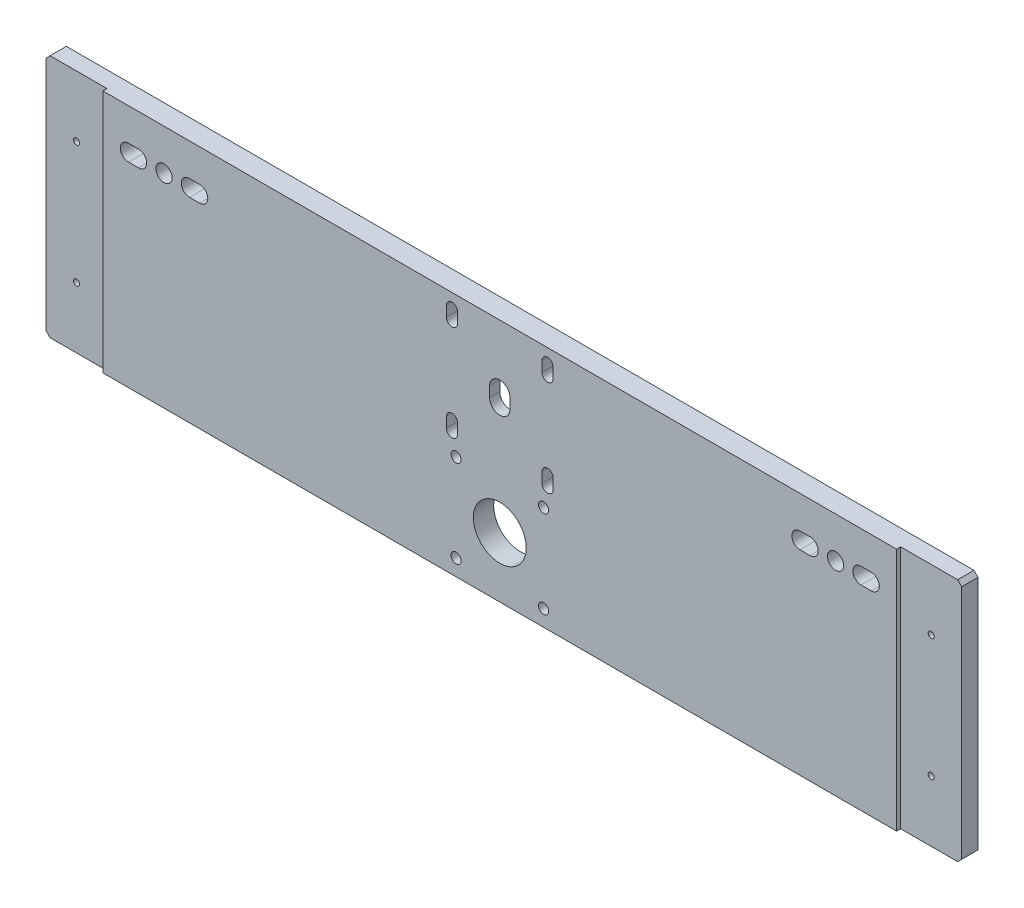
SolidWorks part; units mm, degrees
ref_plane "Piano frontale" through (0, 0, 0) normal (0, 0, 1) x (1, 0, 0)
ref_plane "Piano superiore" through (0, 0, 0) normal (0, 1, 0) x (1, 0, 0)
ref_plane "Piano destro" through (0, 0, 0) normal (1, 0, 0) x (0, 0, -1)
sketch "Schizzo1" plane through (0, 0, 0) normal (0, 0, 1) x (1, 0, 0)
  line L0 (225, 120) -> (225, 0) construction
  line L1 (2, 0) -> (448, 0)
  line L2 (0, 2) -> (0, 118)
  line L3 (2, 120) -> (448, 120)
  line L4 (450, 2) -> (450, 118)
  line L5 (203.5, 52.7163) -> (203.5, 5.9855) construction
  line L6 (250.0723, 51) -> (199.9971, 51) construction
  line L7 (225, 29.5) -> (243.5099, 29.5) construction
  line L8 (459.2931, 100) -> (370.8276, 100) construction
  line L9 (407.5, 100) -> (402.5, 100) construction
  line L10 (407.5, 96) -> (402.5, 96)
  line L11 (407.5, 104) -> (402.5, 104)
  line L12 (377.5, 100) -> (372.5, 100) construction
  line L13 (377.5, 96) -> (372.5, 96)
  line L14 (377.5, 104) -> (372.5, 104)
  line L15 (42.5, 100) -> (47.5, 100) construction
  line L16 (42.5, 96) -> (47.5, 96)
  line L17 (42.5, 104) -> (47.5, 104)
  line L18 (72.5, 100) -> (77.5, 100) construction
  line L19 (72.5, 96) -> (77.5, 96)
  line L20 (72.5, 104) -> (77.5, 104)
  line L21 (0, 118) -> (2, 120)
  line L22 (2, 0) -> (0, 2)
  line L23 (448, 0) -> (450, 2)
  line L24 (448, 120) -> (450, 118)
  line L25 (225, 60) -> (450, 60) construction
  line L26 (267.1703, 87) -> (188.4108, 87) construction
  line L27 (225, 84.5) -> (225, 89.5) construction
  line L28 (220, 84.5) -> (220, 89.5)
  line L29 (230, 84.5) -> (230, 89.5)
  line L30 (201.5, 113.1) -> (201.5, 108.1) construction
  line L31 (204.25, 113.1) -> (204.25, 108.1)
  line L32 (198.75, 113.1) -> (198.75, 108.1)
  line L33 (248.5, 113.1) -> (248.5, 108.1) construction
  line L34 (245.75, 113.1) -> (245.75, 108.1)
  line L35 (251.25, 113.1) -> (251.25, 108.1)
  line L36 (201.5, 60.9) -> (201.5, 65.9) construction
  line L37 (204.25, 60.9) -> (204.25, 65.9)
  line L38 (198.75, 60.9) -> (198.75, 65.9)
  line L39 (248.5, 60.9) -> (248.5, 65.9) construction
  line L40 (245.75, 60.9) -> (245.75, 65.9)
  line L41 (251.25, 60.9) -> (251.25, 65.9)
  circle A0 centre (225, 29.5) radius 13
  arc A1 (407.5, 96) -> (407.5, 104) centre (407.5, 100) ccw
  arc A2 (402.5, 104) -> (402.5, 96) centre (402.5, 100) ccw
  circle A3 centre (390, 100) radius 4
  arc A4 (377.5, 96) -> (377.5, 104) centre (377.5, 100) ccw
  arc A5 (372.5, 104) -> (372.5, 96) centre (372.5, 100) ccw
  arc A6 (42.5, 96) -> (42.5, 104) centre (42.5, 100) cw
  arc A7 (47.5, 104) -> (47.5, 96) centre (47.5, 100) cw
  arc A8 (72.5, 96) -> (72.5, 104) centre (72.5, 100) cw
  arc A9 (77.5, 104) -> (77.5, 96) centre (77.5, 100) cw
  circle A10 centre (60, 100) radius 4
  circle A11 centre (15, 30) radius 1.5
  circle A12 centre (435, 30) radius 1.5
  circle A13 centre (203.5, 51) radius 2.5
  circle A14 centre (246.5, 51) radius 2.5
  circle A15 centre (246.5, 8) radius 2.5
  circle A16 centre (203.5, 8) radius 2.5
  circle A17 centre (435, 90) radius 1.5
  circle A18 centre (15, 90) radius 1.5
  arc A19 (220, 84.5) -> (230, 84.5) centre (225, 84.5) ccw
  arc A20 (230, 89.5) -> (220, 89.5) centre (225, 89.5) ccw
  arc A21 (204.25, 113.1) -> (198.75, 113.1) centre (201.5, 113.1) ccw
  arc A22 (198.75, 108.1) -> (204.25, 108.1) centre (201.5, 108.1) ccw
  arc A23 (245.75, 113.1) -> (251.25, 113.1) centre (248.5, 113.1) cw
  arc A24 (251.25, 108.1) -> (245.75, 108.1) centre (248.5, 108.1) cw
  arc A25 (204.25, 60.9) -> (198.75, 60.9) centre (201.5, 60.9) cw
  arc A26 (198.75, 65.9) -> (204.25, 65.9) centre (201.5, 65.9) cw
  arc A27 (245.75, 60.9) -> (251.25, 60.9) centre (248.5, 60.9) ccw
  arc A28 (251.25, 65.9) -> (245.75, 65.9) centre (248.5, 65.9) ccw
  point P0 (0, 0)
  point P1 (450, 120)
  point P2 (0, 120)
  point P3 (450, 0)
  point P13 (203.5, 51)
  point P14 (246.5, 51)
  point P15 (203.5, 8)
  point P17 (246.5, 8)
  point P22 (405, 100)
  point P31 (375, 100)
  point P38 (45, 100)
  point P45 (75, 100)
  point P80 (225, 87)
  point P83 (225, 87)
  point P90 (201.5, 110.6)
  point P97 (248.5, 110.6)
  point P104 (201.5, 63.4)
  point P111 (248.5, 63.4)
  dimension "D4" = 26
  dimension "D10" = 8
  dimension "D15" = 3
  dimension "D17" = 5
  dimension "D1" = 120
  dimension "D2" = 450
  dimension "D3" = 90.5
  dimension "D5" = 21.5
  dimension "D6" = 21.5
  dimension "D7" = 20
  dimension "D8" = 5
  dimension "D9" = 8
  dimension "D11" = 45
  dimension "D12" = 60
  dimension "D13" = 75
  dimension "D14" = 30
  dimension "D16" = 15
  dimension "D18" = 33
  dimension "D23" = 10
  dimension "D24" = 5
  dimension "D25" = 9.4
  dimension "D26" = 5.5
  dimension "D27" = 5
  dimension "D28" = 23.5
extrude "Estrusione-Estrusione1" add sketch "Schizzo1" against normal blind 10
sketch "Schizzo2" plane through (0, 0, 0) normal (0, 0, 1) x (1, 0, 0)
  line L0 (448, 120) -> (2, 120) construction
  line L1 (30, 120) -> (0, 120)
  line L2 (30, 120) -> (30, 0)
  line L3 (30, 0) -> (0, 0)
  line L4 (0, 120) -> (0, 0)
  line L5 (225, 120) -> (225, -23.5993) construction
  line L6 (450, 120) -> (450, 0)
  line L7 (420, 0) -> (450, 0)
  line L8 (420, 120) -> (420, 0)
  line L9 (420, 120) -> (450, 120)
  dimension "D1" = 30
extrude "Taglio-Estrusione1" cut sketch "Schizzo2" against normal blind 2
sketch "Schizzo3" plane through (0, 0, -10) normal (0, 0, 1) x (1, 0, 0)
  line L0 (225, 120) -> (225, 0) construction
  line L1 (420, 120) -> (30, 120) construction
  line L2 (30, 0) -> (420, 0) construction
  line L3 (-36.0624, 87) -> (457.6758, 87) construction
  line L5 (248.5, 57) -> (201.5, 57)
  line L6 (253.5, 62) -> (253.5, 112)
  line L7 (248.5, 117) -> (201.5, 117)
  line L8 (196.5, 62) -> (196.5, 112)
  line L9 (253.5, 57) -> (196.5, 117) construction
  line L10 (253.5, 117) -> (196.5, 57) construction
  arc A0 (196.5, 112) -> (201.5, 117) centre (201.5, 112) cw
  arc A1 (248.5, 117) -> (253.5, 112) centre (248.5, 112) cw
  arc A2 (253.5, 62) -> (248.5, 57) centre (248.5, 62) cw
  arc A3 (201.5, 57) -> (196.5, 62) centre (201.5, 62) cw
  point P8 (225, 87)
  dimension "D4" = 5
  dimension "D5" = 5
  dimension "D1" = 33
  dimension "D2" = 57
  dimension "D3" = 60
extrude "Taglio-Estrusione2" cut sketch "Schizzo3" along normal blind 3
sketch "Schizzo4" plane through (0, 0, -10) normal (0, 0, 1) x (1, 0, 0)
  line L0 (225, 120) -> (225, 0) construction
  line L1 (420, 120) -> (30, 120) construction
  line L2 (30, 0) -> (420, 0) construction
  line L3 (196.5, 87) -> (253.5, 87) construction
  line L4 (196.5, 112) -> (196.5, 62) construction
  line L5 (253.5, 62) -> (253.5, 112) construction
  line L7 (239.5, 57) -> (210.5, 57)
  line L8 (244.5, 62) -> (244.5, 112)
  line L9 (239.5, 117) -> (210.5, 117)
  line L10 (205.5, 62) -> (205.5, 112)
  line L11 (244.5, 57) -> (205.5, 117) construction
  line L12 (244.5, 117) -> (205.5, 57) construction
  arc A0 (239.5, 117) -> (244.5, 112) centre (239.5, 112) cw
  arc A1 (244.5, 62) -> (239.5, 57) centre (239.5, 62) cw
  arc A2 (210.5, 57) -> (205.5, 62) centre (210.5, 62) cw
  arc A3 (205.5, 112) -> (210.5, 117) centre (210.5, 112) cw
  point P12 (225, 87)
  dimension "D3" = 5
  dimension "D1" = 39
  dimension "D2" = 60
extrude "Taglio-Estrusione5" cut sketch "Schizzo4" along normal blind 5
